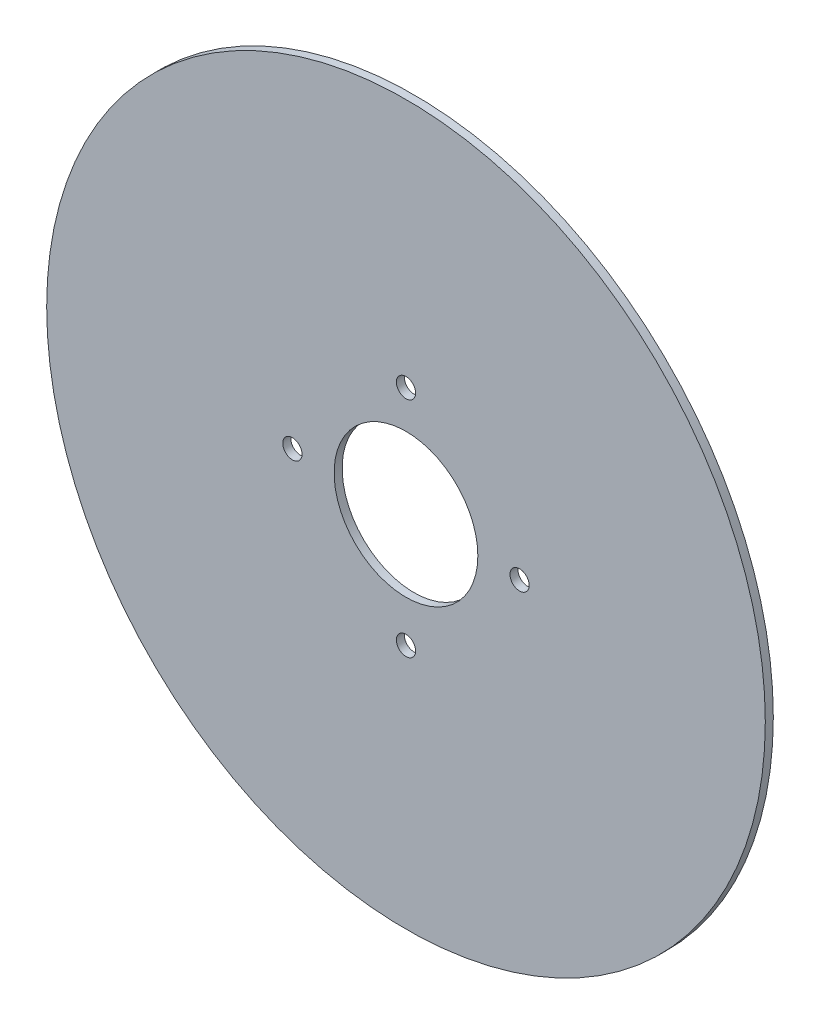
SolidWorks part; units mm, degrees
ref_plane "Front Plane" through (0, 0, 0) normal (0, 0, 1) x (1, 0, 0)
ref_plane "Top Plane" through (0, 0, 0) normal (0, 1, 0) x (1, 0, 0)
ref_plane "Right Plane" through (0, 0, 0) normal (1, 0, 0) x (0, 0, -1)
sketch "Sketch1" plane through (0, 0, 0) normal (0, 0, 1) x (1, 0, 0)
  circle A0 centre (0, 0) radius 11.2
  circle A1 centre (0, 0) radius 56
extrude "Extrude1" add sketch "Sketch1" along normal blind 1.25
sketch "Sketch2" plane through (0, 0, 1.25) normal (0, 0, 1) x (1, 0, 0)
  circle A0 centre (17.7, 0) radius 1.5
  circle A1 centre (0, -17.7) radius 1.5
  circle A2 centre (-17.7, 0) radius 1.5
  circle A3 centre (0, 17.1) radius 1.5
extrude "Extrude2" cut sketch "Sketch2" against normal up to surface (1.25 mm away) up to face at (56, 0, 0)
